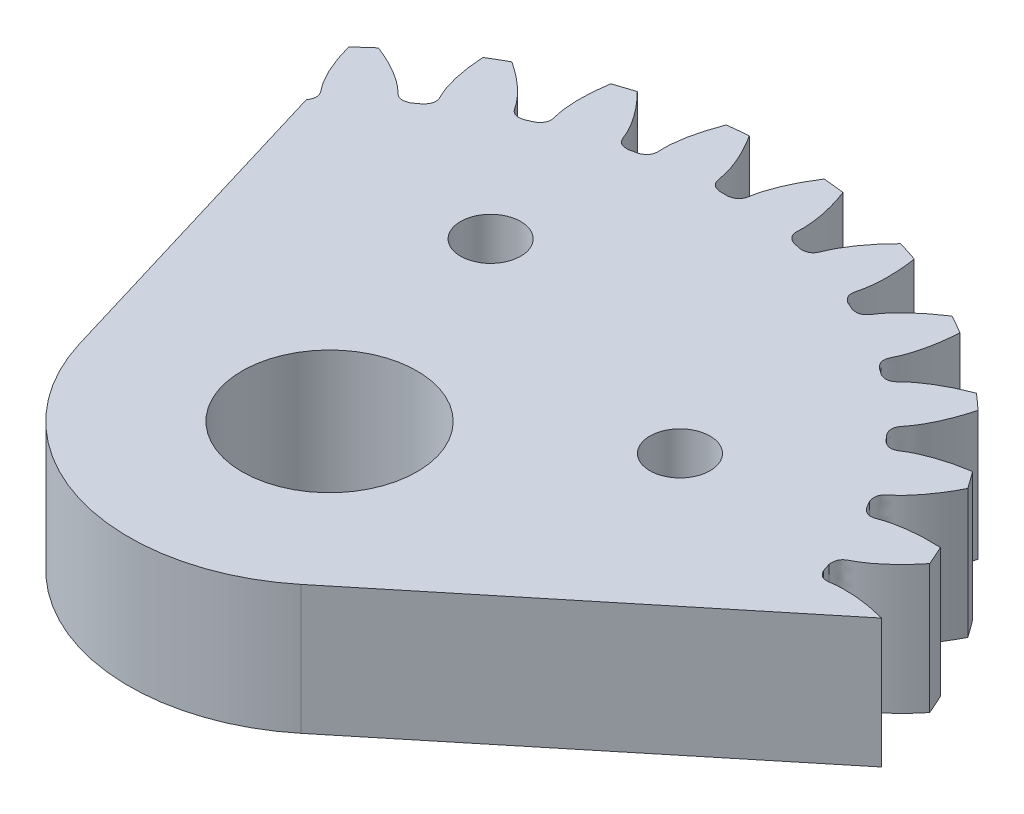
SolidWorks part; units mm, degrees
ref_plane "前视基准面" through (0, 0, 0) normal (0, 0, 1) x (1, 0, 0)
ref_plane "上视基准面" through (0, 0, 0) normal (0, 1, 0) x (1, 0, 0)
ref_plane "右视基准面" through (0, 0, 0) normal (1, 0, 0) x (0, 0, -1)
other "Configuration Table"
sketch "草图2" plane through (0, 0, 0) normal (0, 1, 0) x (1, 0, 0)
  line L0 (-48.308, -1.168) -> (-18.308, -1.168)
  line L1 (-18.308, -1.168) -> (-23.7158, 15.4755) construction
  line L2 (-48.308, -15.168) -> (-18.308, -15.168)
  line L3 (-9.4476, -12.0074) -> (12.8313, 6.2039)
  line L4 (-18.308, -1.168) -> (-4.1502, 9.1183) construction
  line L5 (-12.9002, 15.4755) -> (-18.308, -1.168) construction
  line L6 (-9.558, 13.9875) -> (-18.308, -1.168) construction
  circle A0 centre (-18.308, -1.168) radius 17.5 construction
  circle A1 centre (-23.7158, 15.4755) radius 2.6
  circle A2 centre (-4.1502, 9.1183) radius 2.6
  arc A3 (-16.4787, 16.2362) -> (-9.558, 13.9875) centre (-18.308, -1.168) cw construction
  arc A4 (-8.558, 15.7195) -> (-16.2697, 18.2252) centre (-18.308, -1.168) ccw
  arc A5 (-10.558, 12.2554) -> (-16.6878, 14.2471) centre (-18.308, -1.168) ccw
  arc A6 (-10.558, 12.2554) -> (-8.558, 15.7195) centre (-9.558, 13.9875) ccw
  arc A7 (-16.2697, 18.2252) -> (-16.6878, 14.2471) centre (-16.4787, 16.2362) ccw
  arc A8 (-30.0178, 11.8371) -> (-34.295, 5.9499) centre (-18.308, -1.168) ccw construction
  circle A13 centre (-48.308, -1.168) radius 6.1
  circle A14 centre (-18.308, -1.168) radius 6.1
  arc A15 (-38.5485, 17.4484) -> (-42.2679, 12.3292) centre (-18.308, -1.168) ccw
  arc A16 (-45.091, 12.4574) -> (-48.308, -15.168) centre (-48.308, -1.168) ccw
  arc A17 (-18.308, -15.168) -> (-9.4476, -12.0074) centre (-18.308, -1.168) ccw
  arc A18 (7.9346, 7.0527) -> (7.7547, 7.6064) centre (-18.308, -1.168) ccw
  arc A19 (11.2173, 11.1713) -> (10.6182, 12.517) centre (-18.308, -1.168) ccw
  arc A20 (5.652, 12.3292) -> (5.3608, 12.8334) centre (-18.308, -1.168) ccw
  arc A21 (8.0067, 17.0403) -> (7.1408, 18.2321) centre (-18.308, -1.168) ccw
  arc A22 (2.3222, 17.0158) -> (1.9326, 17.4484) centre (-18.308, -1.168) ccw
  arc A23 (3.6459, 22.1135) -> (2.5512, 23.0992) centre (-18.308, -1.168) ccw
  arc A24 (-1.9093, 20.9076) -> (-2.3803, 21.2499) centre (-18.308, -1.168) ccw
  arc A25 (-1.6743, 26.1692) -> (-2.9501, 26.9058) centre (-18.308, -1.168) ccw
  arc A26 (-6.8574, 23.8347) -> (-7.3893, 24.0715) centre (-18.308, -1.168) ccw
  arc A27 (-7.7215, 29.0302) -> (-9.1226, 29.4854) centre (-18.308, -1.168) ccw
  arc A28 (-12.306, 25.6691) -> (-12.8755, 25.7901) centre (-18.308, -1.168) ccw
  arc A29 (-14.2314, 30.5713) -> (-15.6965, 30.7253) centre (-18.308, -1.168) ccw
  arc A30 (-18.0168, 26.3305) -> (-18.5991, 26.3305) centre (-18.308, -1.168) ccw
  arc A31 (-20.9195, 30.7253) -> (-22.3845, 30.5713) centre (-18.308, -1.168) ccw
  arc A32 (-23.7405, 25.7901) -> (-24.31, 25.6691) centre (-18.308, -1.168) ccw
  arc A33 (-27.4934, 29.4854) -> (-28.8944, 29.0302) centre (-18.308, -1.168) ccw
  arc A34 (-29.2266, 24.0715) -> (-29.7585, 23.8347) centre (-18.308, -1.168) ccw
  arc A35 (-33.6658, 26.9058) -> (-34.9416, 26.1692) centre (-18.308, -1.168) ccw
  arc A36 (-34.2356, 21.2499) -> (-34.7067, 20.9076) centre (-18.308, -1.168) ccw
  arc A37 (-39.1671, 23.0992) -> (-40.2619, 22.1135) centre (-18.308, -1.168) ccw
  spline S0 degree 3 poles (-42.2679, 12.3292) (-42.741, 11.7647) (-43.1486, 11.9953) (-43.6155, 12.1524) (-43.7123, 12.183) (-43.8205, 12.2147) (-43.9402, 12.2473) (-44.0714, 12.2802) (-44.2143, 12.313) (-44.3689, 12.3453) (-44.5351, 12.3765) (-44.7131, 12.4063) (-44.8996, 12.4337) (-45.027, 12.4499) (-45.091, 12.4574) knots 0.548501 0.548501 0.548501 0.548501 0.663825 0.671913 0.681013 0.691124 0.702246 0.714378 0.727522 0.741677 0.756843 0.77302 0.790209 0.807551 0.807551 0.807551 0.807551
  spline S1 degree 3 poles (12.8313, 6.2039) (12.7024, 6.2383) (12.4819, 6.2939) (12.1722, 6.3643) (11.9071, 6.419) (11.6521, 6.4664) (11.4073, 6.5068) (11.1729, 6.5407) (10.9491, 6.5685) (10.736, 6.5906) (10.5337, 6.6076) (10.3424, 6.6198) (10.1621, 6.6276) (9.993, 6.6316) (9.8351, 6.6322) (9.6886, 6.6298) (9.5533, 6.6249) (9.4295, 6.618) (9.317, 6.6094) (9.216, 6.5996) (8.7267, 6.543) (8.28, 6.4022) (7.9346, 7.0527) knots 0 0 0 0 0.035889 0.061166 0.085431 0.108685 0.130929 0.152161 0.172382 0.191592 0.209791 0.22698 0.243157 0.258323 0.272478 0.285622 0.297754 0.308876 0.318987 0.328087 0.336175 0.451499 0.451499 0.451499 0.451499
  spline S2 degree 3 poles (7.7547, 7.6064) (7.6518, 8.3356) (8.0959, 8.4843) (8.5251, 8.7261) (8.6125, 8.7776) (8.7085, 8.8368) (8.8128, 8.9039) (8.9251, 8.9794) (9.0451, 9.0637) (9.1725, 9.1569) (9.307, 9.2596) (9.4482, 9.3719) (9.5958, 9.4942) (9.7495, 9.6268) (9.9089, 9.77) (10.0736, 9.9241) (10.2433, 10.0892) (10.4176, 10.2658) (10.6607, 10.5222) (10.9298, 10.8238) (11.1332, 11.0677) (11.2173, 11.1713) knots 0.548501 0.548501 0.548501 0.548501 0.663825 0.671913 0.681013 0.691124 0.702246 0.714378 0.727522 0.741677 0.756843 0.77302 0.790209 0.808408 0.827618 0.847839 0.869071 0.891315 0.914569 0.964111 1 1 1 1
  spline S3 degree 3 poles (10.6182, 12.517) (10.4849, 12.5239) (10.2576, 12.5324) (9.9401, 12.5369) (9.6694, 12.5353) (9.4101, 12.5286) (9.1623, 12.5172) (8.926, 12.5016) (8.7013, 12.4823) (8.4882, 12.4597) (8.2868, 12.4342) (8.0972, 12.4063) (7.9192, 12.3765) (7.753, 12.3453) (7.5984, 12.313) (7.4555, 12.2802) (7.3243, 12.2473) (7.2046, 12.2147) (7.0964, 12.183) (6.9996, 12.1524) (6.5327, 11.9953) (6.125, 11.7647) (5.652, 12.3292) knots 0 0 0 0 0.035889 0.061166 0.085431 0.108685 0.130929 0.152161 0.172382 0.191592 0.209791 0.22698 0.243157 0.258323 0.272478 0.285622 0.297754 0.308876 0.318987 0.328087 0.336175 0.451499 0.451499 0.451499 0.451499
  spline S4 degree 3 poles (5.3608, 12.8334) (5.1086, 13.5253) (5.5121, 13.763) (5.8816, 14.0888) (5.9565, 14.1573) (6.0381, 14.2352) (6.1261, 14.3225) (6.2203, 14.4198) (6.3201, 14.5271) (6.4253, 14.6448) (6.5355, 14.7732) (6.6503, 14.9124) (6.7692, 15.0627) (6.892, 15.2244) (7.0181, 15.3976) (7.1472, 15.5825) (7.2789, 15.7794) (7.4127, 15.9883) (7.5972, 16.2897) (7.7976, 16.6406) (7.9459, 16.9215) (8.0067, 17.0403) knots 0.548501 0.548501 0.548501 0.548501 0.663825 0.671913 0.681013 0.691124 0.702246 0.714378 0.727522 0.741677 0.756843 0.77302 0.790209 0.808408 0.827618 0.847839 0.869071 0.891315 0.914569 0.964111 1 1 1 1
  spline S5 degree 3 poles (7.1408, 18.2321) (7.009, 18.211) (6.7849, 18.1722) (6.4734, 18.1105) (6.209, 18.0527) (5.9567, 17.9922) (5.7167, 17.9296) (5.4888, 17.8652) (5.273, 17.7995) (5.0693, 17.7331) (4.8776, 17.6663) (4.6979, 17.5996) (4.53, 17.5335) (4.3739, 17.4684) (4.2294, 17.4047) (4.0965, 17.3429) (3.9749, 17.2834) (3.8646, 17.2267) (3.7654, 17.1731) (3.6771, 17.1231) (3.2531, 16.8723) (2.9023, 16.562) (2.3222, 17.0158) knots 0 0 0 0 0.035889 0.061166 0.085431 0.108685 0.130929 0.152161 0.172382 0.191592 0.209791 0.22698 0.243157 0.258323 0.272478 0.285622 0.297754 0.308876 0.318987 0.328087 0.336175 0.451499 0.451499 0.451499 0.451499
  spline S6 degree 3 poles (1.9326, 17.4484) (1.542, 18.0728) (1.8872, 18.3892) (2.1809, 18.7847) (2.2399, 18.8673) (2.3036, 18.9604) (2.3715, 19.0642) (2.4434, 19.1788) (2.5187, 19.3046) (2.5972, 19.4416) (2.6783, 19.5901) (2.7616, 19.7501) (2.8467, 19.9219) (2.9331, 20.1056) (3.0205, 20.3012) (3.1084, 20.5089) (3.1962, 20.7288) (3.2836, 20.961) (3.4015, 21.2941) (3.5245, 21.6791) (3.6112, 21.9847) (3.6459, 22.1135) knots 0.548501 0.548501 0.548501 0.548501 0.663825 0.671913 0.681013 0.691124 0.702246 0.714378 0.727522 0.741677 0.756843 0.77302 0.790209 0.808408 0.827618 0.847839 0.869071 0.891315 0.914569 0.964111 1 1 1 1
  spline S7 degree 3 poles (2.5512, 23.0992) (2.4267, 23.0512) (2.2156, 22.9667) (1.9236, 22.8416) (1.677, 22.73) (1.4429, 22.6184) (1.2211, 22.5072) (1.0116, 22.3969) (0.8141, 22.2878) (0.6287, 22.1805) (0.4551, 22.0753) (0.2932, 21.9727) (0.1427, 21.8731) (0.0035, 21.7769) (-0.1245, 21.6846) (-0.2417, 21.5965) (-0.3483, 21.5131) (-0.4444, 21.4346) (-0.5303, 21.3616) (-0.6063, 21.2943) (-0.9689, 20.9609) (-1.2475, 20.5844) (-1.9093, 20.9076) knots 0 0 0 0 0.035889 0.061166 0.085431 0.108685 0.130929 0.152161 0.172382 0.191592 0.209791 0.22698 0.243157 0.258323 0.272478 0.285622 0.297754 0.308876 0.318987 0.328087 0.336175 0.451499 0.451499 0.451499 0.451499
  spline S8 degree 3 poles (-2.3803, 21.2499) (-2.8922, 21.7794) (-2.6203, 22.1607) (-2.4152, 22.6086) (-2.3747, 22.7016) (-2.3318, 22.8059) (-2.2869, 22.9216) (-2.2404, 23.0487) (-2.1929, 23.1873) (-2.1446, 23.3377) (-2.0962, 23.4997) (-2.048, 23.6736) (-2.0004, 23.8593) (-1.954, 24.0569) (-1.9092, 24.2665) (-1.8665, 24.4879) (-1.8263, 24.7213) (-1.7891, 24.9666) (-1.7431, 25.3169) (-1.7027, 25.7191) (-1.6815, 26.036) (-1.6743, 26.1692) knots 0.548501 0.548501 0.548501 0.548501 0.663825 0.671913 0.681013 0.691124 0.702246 0.714378 0.727522 0.741677 0.756843 0.77302 0.790209 0.808408 0.827618 0.847839 0.869071 0.891315 0.914569 0.964111 1 1 1 1
  spline S9 degree 3 poles (-2.9501, 26.9058) (-3.0619, 26.833) (-3.2508, 26.7063) (-3.5104, 26.5233) (-3.7284, 26.3629) (-3.9342, 26.2051) (-4.128, 26.0502) (-4.31, 25.8987) (-4.4804, 25.751) (-4.6395, 25.6074) (-4.7875, 25.4684) (-4.9245, 25.3344) (-5.051, 25.2057) (-5.1671, 25.0827) (-5.2732, 24.9658) (-5.3695, 24.8553) (-5.4564, 24.7515) (-5.5341, 24.6548) (-5.6029, 24.5655) (-5.6633, 24.4838) (-5.9486, 24.0823) (-6.1429, 23.6562) (-6.8574, 23.8347) knots 0 0 0 0 0.035889 0.061166 0.085431 0.108685 0.130929 0.152161 0.172382 0.191592 0.209791 0.22698 0.243157 0.258323 0.272478 0.285622 0.297754 0.308876 0.318987 0.328087 0.336175 0.451499 0.451499 0.451499 0.451499
  spline S10 degree 3 poles (-7.3893, 24.0715) (-8.0001, 24.483) (-7.8134, 24.9125) (-7.7059, 25.3933) (-7.6856, 25.4927) (-7.6654, 25.6037) (-7.6455, 25.7261) (-7.6265, 25.8601) (-7.6088, 26.0056) (-7.5928, 26.1627) (-7.5791, 26.3313) (-7.5681, 26.5114) (-7.5602, 26.703) (-7.556, 26.9059) (-7.5557, 27.1202) (-7.56, 27.3457) (-7.5692, 27.5823) (-7.5838, 27.83) (-7.6116, 28.1822) (-7.6557, 28.5839) (-7.7008, 28.8984) (-7.7215, 29.0302) knots 0.548501 0.548501 0.548501 0.548501 0.663825 0.671913 0.681013 0.691124 0.702246 0.714378 0.727522 0.741677 0.756843 0.77302 0.790209 0.808408 0.827618 0.847839 0.869071 0.891315 0.914569 0.964111 1 1 1 1
  spline S11 degree 3 poles (-9.1226, 29.4854) (-9.2168, 29.3909) (-9.3752, 29.2278) (-9.5911, 28.9948) (-9.771, 28.7926) (-9.9395, 28.5954) (-10.0969, 28.4036) (-10.2434, 28.2176) (-10.3794, 28.0376) (-10.5051, 27.8641) (-10.6209, 27.6974) (-10.7272, 27.5378) (-10.8241, 27.3857) (-10.9121, 27.2412) (-10.9916, 27.1048) (-11.0628, 26.9766) (-11.1262, 26.8571) (-11.182, 26.7463) (-11.2308, 26.6447) (-11.2729, 26.5523) (-11.4685, 26.1002) (-11.57, 25.643) (-12.306, 25.6691) knots 0 0 0 0 0.035889 0.061166 0.085431 0.108685 0.130929 0.152161 0.172382 0.191592 0.209791 0.22698 0.243157 0.258323 0.272478 0.285622 0.297754 0.308876 0.318987 0.328087 0.336175 0.451499 0.451499 0.451499 0.451499
  spline S12 degree 3 poles (-12.8755, 25.7901) (-13.5585, 26.0656) (-13.4651, 26.5246) (-13.46, 27.0172) (-13.4608, 27.1186) (-13.4641, 27.2314) (-13.4701, 27.3553) (-13.4793, 27.4903) (-13.4923, 27.6363) (-13.5094, 27.7933) (-13.531, 27.961) (-13.5577, 28.1395) (-13.5898, 28.3285) (-13.6278, 28.5279) (-13.6721, 28.7375) (-13.7232, 28.9572) (-13.7814, 29.1868) (-13.8471, 29.426) (-13.9476, 29.7648) (-14.0743, 30.1485) (-14.1838, 30.4467) (-14.2314, 30.5713) knots 0.548501 0.548501 0.548501 0.548501 0.663825 0.671913 0.681013 0.691124 0.702246 0.714378 0.727522 0.741677 0.756843 0.77302 0.790209 0.808408 0.827618 0.847839 0.869071 0.891315 0.914569 0.964111 1 1 1 1
  spline S13 degree 3 poles (-15.6965, 30.7253) (-15.769, 30.6133) (-15.8901, 30.4208) (-16.0527, 30.148) (-16.1867, 29.9128) (-16.3105, 29.6849) (-16.4246, 29.4646) (-16.5292, 29.2521) (-16.6248, 29.0479) (-16.7117, 28.852) (-16.7904, 28.6649) (-16.8611, 28.4867) (-16.9243, 28.3177) (-16.9803, 28.1581) (-17.0297, 28.0081) (-17.0727, 27.868) (-17.1098, 27.7378) (-17.1415, 27.6179) (-17.1681, 27.5083) (-17.19, 27.4092) (-17.2874, 26.9263) (-17.2915, 26.458) (-18.0168, 26.3305) knots 0 0 0 0 0.035889 0.061166 0.085431 0.108685 0.130929 0.152161 0.172382 0.191592 0.209791 0.22698 0.243157 0.258323 0.272478 0.285622 0.297754 0.308876 0.318987 0.328087 0.336175 0.451499 0.451499 0.451499 0.451499
  spline S14 degree 3 poles (-18.5991, 26.3305) (-19.3244, 26.458) (-19.3286, 26.9263) (-19.4259, 27.4092) (-19.4479, 27.5083) (-19.4745, 27.6179) (-19.5061, 27.7378) (-19.5432, 27.868) (-19.5863, 28.0081) (-19.6356, 28.1581) (-19.6917, 28.3177) (-19.7548, 28.4867) (-19.8256, 28.6649) (-19.9042, 28.852) (-19.9911, 29.0479) (-20.0867, 29.2521) (-20.1914, 29.4646) (-20.3054, 29.6849) (-20.4741, 29.9954) (-20.6778, 30.3444) (-20.8469, 30.6133) (-20.9195, 30.7253) knots 0.548501 0.548501 0.548501 0.548501 0.663825 0.671913 0.681013 0.691124 0.702246 0.714378 0.727522 0.741677 0.756843 0.77302 0.790209 0.808408 0.827618 0.847839 0.869071 0.891315 0.914569 0.964111 1 1 1 1
  spline S15 degree 3 poles (-22.3845, 30.5713) (-22.4322, 30.4467) (-22.5106, 30.2332) (-22.613, 29.9325) (-22.6951, 29.6747) (-22.7688, 29.426) (-22.8346, 29.1868) (-22.8928, 28.9572) (-22.9438, 28.7375) (-22.9881, 28.5279) (-23.0261, 28.3285) (-23.0583, 28.1395) (-23.0849, 27.961) (-23.1066, 27.7933) (-23.1237, 27.6363) (-23.1366, 27.4903) (-23.1459, 27.3553) (-23.1519, 27.2314) (-23.1551, 27.1186) (-23.156, 27.0172) (-23.1508, 26.5246) (-23.0575, 26.0656) (-23.7405, 25.7901) knots 0 0 0 0 0.035889 0.061166 0.085431 0.108685 0.130929 0.152161 0.172382 0.191592 0.209791 0.22698 0.243157 0.258323 0.272478 0.285622 0.297754 0.308876 0.318987 0.328087 0.336175 0.451499 0.451499 0.451499 0.451499
  spline S16 degree 3 poles (-24.31, 25.6691) (-25.046, 25.643) (-25.1474, 26.1002) (-25.343, 26.5523) (-25.3851, 26.6447) (-25.4339, 26.7463) (-25.4898, 26.8571) (-25.5531, 26.9766) (-25.6244, 27.1048) (-25.7038, 27.2412) (-25.7918, 27.3857) (-25.8888, 27.5378) (-25.995, 27.6974) (-26.1108, 27.8641) (-26.2366, 28.0376) (-26.3725, 28.2176) (-26.5191, 28.4036) (-26.6765, 28.5954) (-26.906, 28.864) (-27.1778, 29.1631) (-27.3992, 29.3909) (-27.4934, 29.4854) knots 0.548501 0.548501 0.548501 0.548501 0.663825 0.671913 0.681013 0.691124 0.702246 0.714378 0.727522 0.741677 0.756843 0.77302 0.790209 0.808408 0.827618 0.847839 0.869071 0.891315 0.914569 0.964111 1 1 1 1
  spline S17 degree 3 poles (-28.8944, 29.0302) (-28.9151, 28.8984) (-28.9474, 28.6732) (-28.9851, 28.3579) (-29.0118, 28.0885) (-29.0322, 27.83) (-29.0468, 27.5823) (-29.056, 27.3457) (-29.0602, 27.1202) (-29.06, 26.9059) (-29.0557, 26.703) (-29.0478, 26.5114) (-29.0368, 26.3313) (-29.0231, 26.1627) (-29.0072, 26.0056) (-28.9895, 25.8601) (-28.9705, 25.7261) (-28.9506, 25.6037) (-28.9303, 25.4927) (-28.91, 25.3933) (-28.8026, 24.9125) (-28.6159, 24.483) (-29.2266, 24.0715) knots 0 0 0 0 0.035889 0.061166 0.085431 0.108685 0.130929 0.152161 0.172382 0.191592 0.209791 0.22698 0.243157 0.258323 0.272478 0.285622 0.297754 0.308876 0.318987 0.328087 0.336175 0.451499 0.451499 0.451499 0.451499
  spline S18 degree 3 poles (-29.7585, 23.8347) (-30.473, 23.6562) (-30.6673, 24.0823) (-30.9527, 24.4838) (-31.013, 24.5655) (-31.0819, 24.6548) (-31.1596, 24.7515) (-31.2464, 24.8553) (-31.3427, 24.9658) (-31.4488, 25.0827) (-31.5649, 25.2057) (-31.6914, 25.3344) (-31.8285, 25.4684) (-31.9764, 25.6074) (-32.1355, 25.751) (-32.3059, 25.8987) (-32.4879, 26.0502) (-32.6817, 26.2051) (-32.9621, 26.4201) (-33.2902, 26.6561) (-33.554, 26.833) (-33.6658, 26.9058) knots 0.548501 0.548501 0.548501 0.548501 0.663825 0.671913 0.681013 0.691124 0.702246 0.714378 0.727522 0.741677 0.756843 0.77302 0.790209 0.808408 0.827618 0.847839 0.869071 0.891315 0.914569 0.964111 1 1 1 1
  spline S19 degree 3 poles (-34.9416, 26.1692) (-34.9345, 26.036) (-34.9192, 25.8091) (-34.8905, 25.4928) (-34.8606, 25.2238) (-34.8268, 24.9666) (-34.7896, 24.7213) (-34.7494, 24.4879) (-34.7067, 24.2665) (-34.6619, 24.0569) (-34.6155, 23.8593) (-34.568, 23.6736) (-34.5198, 23.4997) (-34.4713, 23.3377) (-34.4231, 23.1873) (-34.3755, 23.0487) (-34.3291, 22.9216) (-34.2842, 22.8059) (-34.2412, 22.7016) (-34.2007, 22.6086) (-33.9957, 22.1607) (-33.7238, 21.7794) (-34.2356, 21.2499) knots 0 0 0 0 0.035889 0.061166 0.085431 0.108685 0.130929 0.152161 0.172382 0.191592 0.209791 0.22698 0.243157 0.258323 0.272478 0.285622 0.297754 0.308876 0.318987 0.328087 0.336175 0.451499 0.451499 0.451499 0.451499
  spline S20 degree 3 poles (-34.7067, 20.9076) (-35.3684, 20.5844) (-35.6471, 20.9609) (-36.0097, 21.2943) (-36.0856, 21.3616) (-36.1716, 21.4346) (-36.2677, 21.5131) (-36.3742, 21.5965) (-36.4914, 21.6846) (-36.6195, 21.7769) (-36.7586, 21.8731) (-36.9091, 21.9727) (-37.071, 22.0753) (-37.2446, 22.1805) (-37.4301, 22.2878) (-37.6275, 22.3969) (-37.837, 22.5072) (-38.0588, 22.6184) (-38.3778, 22.7705) (-38.7477, 22.9331) (-39.0426, 23.0512) (-39.1671, 23.0992) knots 0.548501 0.548501 0.548501 0.548501 0.663825 0.671913 0.681013 0.691124 0.702246 0.714378 0.727522 0.741677 0.756843 0.77302 0.790209 0.808408 0.827618 0.847839 0.869071 0.891315 0.914569 0.964111 1 1 1 1
  spline S21 degree 3 poles (-40.2619, 22.1135) (-40.2271, 21.9847) (-40.1651, 21.7659) (-40.0712, 21.4625) (-39.9861, 21.2056) (-39.8995, 20.961) (-39.8121, 20.7288) (-39.7243, 20.5089) (-39.6365, 20.3012) (-39.5491, 20.1056) (-39.4626, 19.9219) (-39.3775, 19.7501) (-39.2942, 19.5901) (-39.2131, 19.4416) (-39.1347, 19.3046) (-39.0593, 19.1788) (-38.9874, 19.0642) (-38.9195, 18.9604) (-38.8558, 18.8673) (-38.7969, 18.7847) (-38.5032, 18.3892) (-38.1579, 18.0728) (-38.5485, 17.4484) knots 0 0 0 0 0.035889 0.061166 0.085431 0.108685 0.130929 0.152161 0.172382 0.191592 0.209791 0.22698 0.243157 0.258323 0.272478 0.285622 0.297754 0.308876 0.318987 0.328087 0.336175 0.451499 0.451499 0.451499 0.451499
  point P32 (-12.9002, 15.4755)
  point P65 (-32.4658, 9.1183)
  dimension "D1" = 35
  dimension "D3" = 5.2
  dimension "D5" = 5.2
  dimension "D7" = 2
  dimension "D2" = 72
  dimension "D4" = 72
  dimension "D6" = 36
  dimension "D8" = 12
extrude "凸台-拉伸1" add sketch "草图2" along normal blind 9 contours A37 S21 A15 S0 A16 L2 A17 L3 S1 A18 S2 A19 S3 A20 S4 A21 S5 A22 S6 A23 S7 A24 S8 A25 S9 A26 S10 A27 S11 A28 S12 A29 S13 A30 S14 A31 S15 A32 S16 A33 S17 A34 S18 A35 S19 A36 S20 region at (-25.179, 0, -5.1379)
sketch "草图3" plane through (0, 9, 0) normal (0, 1, 0) x (1, 0, 0)
  line L0 (-38.5485, 17.4484) -> (-31.7111, -5.2121)
  line L2 (-48.308, -15.168) -> (-18.308, -15.168)
  line L3 (-9.4476, -12.0074) -> (12.8313, 6.2039)
  line L4 (-48.308, -15.168) -> (-18.308, -15.168)
  line L5 (-9.4476, -12.0074) -> (12.8313, 6.2039)
  circle A0 centre (-18.308, -1.168) radius 6.1 construction
  circle A1 centre (-18.308, -1.168) radius 6.1
  circle A2 centre (-18.308, -1.168) radius 14
  arc A23 (-39.1671, 23.0992) -> (-40.2619, 22.1135) centre (-18.308, -1.168) ccw
  arc A24 (-38.5485, 17.4484) -> (-42.2679, 12.3292) centre (-18.308, -1.168) ccw
  arc A25 (-45.091, 12.4574) -> (-48.308, -15.168) centre (-48.308, -1.168) ccw
  arc A26 (-18.308, -15.168) -> (-9.4476, -12.0074) centre (-18.308, -1.168) ccw
  arc A27 (7.9346, 7.0527) -> (7.7547, 7.6064) centre (-18.308, -1.168) ccw
  arc A28 (11.2173, 11.1713) -> (10.6182, 12.517) centre (-18.308, -1.168) ccw
  arc A29 (5.652, 12.3292) -> (5.3608, 12.8334) centre (-18.308, -1.168) ccw
  arc A30 (8.0067, 17.0403) -> (7.1408, 18.2321) centre (-18.308, -1.168) ccw
  arc A31 (2.3222, 17.0158) -> (1.9326, 17.4484) centre (-18.308, -1.168) ccw
  arc A32 (3.6459, 22.1135) -> (2.5512, 23.0992) centre (-18.308, -1.168) ccw
  arc A33 (-1.9093, 20.9076) -> (-2.3803, 21.2499) centre (-18.308, -1.168) ccw
  arc A34 (-1.6743, 26.1692) -> (-2.9501, 26.9058) centre (-18.308, -1.168) ccw
  arc A35 (-6.8574, 23.8347) -> (-7.3893, 24.0715) centre (-18.308, -1.168) ccw
  arc A36 (-7.7215, 29.0302) -> (-9.1226, 29.4854) centre (-18.308, -1.168) ccw
  arc A37 (-12.306, 25.6691) -> (-12.8755, 25.7901) centre (-18.308, -1.168) ccw
  arc A38 (-14.2314, 30.5713) -> (-15.6965, 30.7253) centre (-18.308, -1.168) ccw
  arc A39 (-18.0168, 26.3305) -> (-18.5991, 26.3305) centre (-18.308, -1.168) ccw
  arc A40 (-20.9195, 30.7253) -> (-22.3845, 30.5713) centre (-18.308, -1.168) ccw
  arc A41 (-23.7405, 25.7901) -> (-24.31, 25.6691) centre (-18.308, -1.168) ccw
  arc A42 (-27.4934, 29.4854) -> (-28.8944, 29.0302) centre (-18.308, -1.168) ccw
  arc A43 (-29.2266, 24.0715) -> (-29.7585, 23.8347) centre (-18.308, -1.168) ccw
  arc A44 (-33.6658, 26.9058) -> (-34.9416, 26.1692) centre (-18.308, -1.168) ccw
  arc A45 (-34.2356, 21.2499) -> (-34.7067, 20.9076) centre (-18.308, -1.168) ccw
  arc A46 (-39.1671, 23.0992) -> (-40.2619, 22.1135) centre (-18.308, -1.168) ccw
  arc A47 (-38.5485, 17.4484) -> (-42.2679, 12.3292) centre (-18.308, -1.168) ccw
  arc A48 (-45.091, 12.4574) -> (-48.308, -15.168) centre (-48.308, -1.168) ccw
  arc A49 (-18.308, -15.168) -> (-9.4476, -12.0074) centre (-18.308, -1.168) ccw
  arc A50 (7.9346, 7.0527) -> (7.7547, 7.6064) centre (-18.308, -1.168) ccw
  arc A51 (11.2173, 11.1713) -> (10.6182, 12.517) centre (-18.308, -1.168) ccw
  arc A52 (5.652, 12.3292) -> (5.3608, 12.8334) centre (-18.308, -1.168) ccw
  arc A53 (8.0067, 17.0403) -> (7.1408, 18.2321) centre (-18.308, -1.168) ccw
  arc A54 (2.3222, 17.0158) -> (1.9326, 17.4484) centre (-18.308, -1.168) ccw
  arc A55 (3.6459, 22.1135) -> (2.5512, 23.0992) centre (-18.308, -1.168) ccw
  arc A56 (-1.9093, 20.9076) -> (-2.3803, 21.2499) centre (-18.308, -1.168) ccw
  arc A57 (-1.6743, 26.1692) -> (-2.9501, 26.9058) centre (-18.308, -1.168) ccw
  arc A58 (-6.8574, 23.8347) -> (-7.3893, 24.0715) centre (-18.308, -1.168) ccw
  arc A59 (-7.7215, 29.0302) -> (-9.1226, 29.4854) centre (-18.308, -1.168) ccw
  arc A60 (-12.306, 25.6691) -> (-12.8755, 25.7901) centre (-18.308, -1.168) ccw
  arc A61 (-14.2314, 30.5713) -> (-15.6965, 30.7253) centre (-18.308, -1.168) ccw
  arc A62 (-18.0168, 26.3305) -> (-18.5991, 26.3305) centre (-18.308, -1.168) ccw
  arc A63 (-20.9195, 30.7253) -> (-22.3845, 30.5713) centre (-18.308, -1.168) ccw
  arc A64 (-23.7405, 25.7901) -> (-24.31, 25.6691) centre (-18.308, -1.168) ccw
  arc A65 (-27.4934, 29.4854) -> (-28.8944, 29.0302) centre (-18.308, -1.168) ccw
  arc A66 (-29.2266, 24.0715) -> (-29.7585, 23.8347) centre (-18.308, -1.168) ccw
  arc A67 (-33.6658, 26.9058) -> (-34.9416, 26.1692) centre (-18.308, -1.168) ccw
  arc A68 (-34.2356, 21.2499) -> (-34.7067, 20.9076) centre (-18.308, -1.168) ccw
  spline S22 degree 3 poles (-2808.7731, -2864.6652) (154.4229, 178.0688) (-54.0437, 66.6203) (-40.0712, 21.4625) (-39.9861, 21.2056) (-39.8995, 20.961) (-39.8121, 20.7288) (-39.7243, 20.5089) (-39.6365, 20.3012) (-39.5491, 20.1056) (-39.4626, 19.9219) (-39.3775, 19.7501) (-39.2942, 19.5901) (-39.2131, 19.4416) (-39.1347, 19.3046) (-39.0593, 19.1788) (-38.9874, 19.0642) (-38.9195, 18.9604) (-38.8558, 18.8673) (-38.7969, 18.7847) (-34.47, 12.9588) (-12.3892, 20.0165) (-3637.1494, -1726.3063) knots -12.628781 -12.628781 -12.628781 -12.628781 0.035889 0.061166 0.085431 0.108685 0.130929 0.152161 0.172382 0.191592 0.209791 0.22698 0.243157 0.258323 0.272478 0.285622 0.297754 0.308876 0.318987 0.328087 0.336175 2.271088 2.271088 2.271088 2.271088 only from (-40.2619, 22.1135) to (-38.5485, 17.4484)
  spline S23 degree 3 poles (504.2173, 3974.4238) (-36.6266, -13.3464) (-36.7373, 9.8375) (-43.6155, 12.1524) (-43.7123, 12.183) (-43.8205, 12.2147) (-43.9402, 12.2473) (-44.0714, 12.2802) (-44.2143, 12.313) (-44.3689, 12.3453) (-44.5351, 12.3765) (-44.7131, 12.4063) (-77.1597, 17.1715) (-131.5858, -139.3296) (1832.491, 3544.1954) knots -1.271213 -1.271213 -1.271213 -1.271213 0.663825 0.671913 0.681013 0.691124 0.702246 0.714378 0.727522 0.741677 0.756843 0.77302 0.790209 9.577619 9.577619 9.577619 9.577619 only from (-42.2679, 12.3292) to (-45.091, 12.4574)
  spline S24 degree 3 poles (-1102.9367, 3847.1943) (50.5502, -240.3757) (58.2663, -4.114) (12.1722, 6.3643) (11.9071, 6.419) (11.6521, 6.4664) (11.4073, 6.5068) (11.1729, 6.5407) (10.9491, 6.5685) (10.736, 6.5906) (10.5337, 6.6076) (10.3424, 6.6198) (10.1621, 6.6276) (9.993, 6.6316) (9.8351, 6.6322) (9.6886, 6.6298) (9.5533, 6.6249) (9.4295, 6.618) (9.317, 6.6094) (9.216, 6.5996) (2.0072, 5.7654) (-2.921, -16.886) (297.0991, 3995.4098) knots -12.628781 -12.628781 -12.628781 -12.628781 0.035889 0.061166 0.085431 0.108685 0.130929 0.152161 0.172382 0.191592 0.209791 0.22698 0.243157 0.258323 0.272478 0.285622 0.297754 0.308876 0.318987 0.328087 0.336175 2.271088 2.271088 2.271088 2.271088 only from (12.8313, 6.2039) to (7.9346, 7.0527)
  spline S25 degree 3 poles (2586.3817, -3049.5365) (-15.1002, 20.5939) (2.2024, 5.1636) (8.5251, 8.7261) (8.6125, 8.7776) (8.7085, 8.8368) (8.8128, 8.9039) (8.9251, 8.9794) (9.0451, 9.0637) (9.1725, 9.1569) (9.307, 9.2596) (9.4482, 9.3719) (9.5958, 9.4942) (9.7495, 9.6268) (9.9089, 9.77) (10.0736, 9.9241) (10.2433, 10.0892) (10.4176, 10.2658) (10.6607, 10.5222) (42.3769, 46.0814) (-104.8979, 234.9145) (1366.3354, -3752.1377) knots -1.271185 -1.271185 -1.271185 -1.271185 0.663825 0.671913 0.681013 0.691124 0.702246 0.714378 0.727522 0.741677 0.756843 0.77302 0.790209 0.808408 0.827618 0.847839 0.869071 0.891315 0.914569 0.964111 13.705364 13.705364 13.705364 13.705364 only from (7.7547, 7.6064) to (11.2173, 11.1713)
  spline S26 degree 3 poles (-1879.3545, 3537.5914) (98.7795, -220.832) (57.2054, 11.8711) (9.9401, 12.5369) (9.6694, 12.5353) (9.4101, 12.5286) (9.1623, 12.5172) (8.926, 12.5016) (8.7013, 12.4823) (8.4882, 12.4597) (8.2868, 12.4342) (8.0972, 12.4063) (7.9192, 12.3765) (7.753, 12.3453) (7.5984, 12.313) (7.4555, 12.2802) (7.3243, 12.2473) (7.2046, 12.2147) (7.0964, 12.183) (6.9996, 12.1524) (0.1218, 9.8377) (0.0107, -13.3434) (-540.7285, 3973.6518) knots -12.628781 -12.628781 -12.628781 -12.628781 0.035889 0.061166 0.085431 0.108685 0.130929 0.152161 0.172382 0.191592 0.209791 0.22698 0.243157 0.258323 0.272478 0.285622 0.297754 0.308876 0.318987 0.328087 0.336175 2.271088 2.271088 2.271088 2.271088 only from (10.6182, 12.517) to (5.652, 12.3292)
  spline S27 degree 3 poles (3163.2544, -2441.3769) (-19.6949, 20.7853) (0.4378, 9.2896) (5.8816, 14.0888) (5.9565, 14.1573) (6.0381, 14.2352) (6.1261, 14.3225) (6.2203, 14.4198) (6.3201, 14.5271) (6.4253, 14.6448) (6.5355, 14.7732) (6.6503, 14.9124) (6.7692, 15.0627) (6.892, 15.2244) (7.0181, 15.3976) (7.1472, 15.5825) (7.2789, 15.7794) (7.4127, 15.9883) (7.5972, 16.2897) (31.2271, 57.666) (-152.09, 211.7525) (2115.9481, -3382.2865) knots -1.271185 -1.271185 -1.271185 -1.271185 0.663825 0.671913 0.681013 0.691124 0.702246 0.714378 0.727522 0.741677 0.756843 0.77302 0.790209 0.808408 0.827618 0.847839 0.869071 0.891315 0.914569 0.964111 13.705364 13.705364 13.705364 13.705364 only from (5.3608, 12.8334) to (8.0067, 17.0403)
  spline S28 degree 3 poles (-2574.4356, 3073.3277) (141.8916, -191.6879) (52.8443, 27.2862) (6.4734, 18.1105) (6.209, 18.0527) (5.9567, 17.9922) (5.7167, 17.9296) (5.4888, 17.8652) (5.273, 17.7995) (5.0693, 17.7331) (4.8776, 17.6663) (4.6979, 17.5996) (4.53, 17.5335) (4.3739, 17.4684) (4.2294, 17.4047) (4.0965, 17.3429) (3.9749, 17.2834) (3.8646, 17.2267) (3.7654, 17.1731) (3.6771, 17.1231) (-2.5692, 13.4289) (2.1418, -9.2687) (-1355.7239, 3778.1751) knots -12.628781 -12.628781 -12.628781 -12.628781 0.035889 0.061166 0.085431 0.108685 0.130929 0.152161 0.172382 0.191592 0.209791 0.22698 0.243157 0.258323 0.272478 0.285622 0.297754 0.308876 0.318987 0.328087 0.336175 2.271088 2.271088 2.271088 2.271088 only from (7.1408, 18.2321) to (2.3222, 17.0158)
  spline S29 degree 3 poles (3601.0776, -1726.5685) (-24.2289, 20.0172) (-2.1461, 12.9585) (2.1809, 18.7847) (2.2399, 18.8673) (2.3036, 18.9604) (2.3715, 19.0642) (2.4434, 19.1788) (2.5187, 19.3046) (2.5972, 19.4416) (2.6783, 19.5901) (2.7616, 19.7501) (2.8467, 19.9219) (2.9331, 20.1056) (3.0205, 20.3012) (3.1084, 20.5089) (3.1962, 20.7288) (3.2836, 20.961) (3.4015, 21.2941) (17.9124, 66.6792) (-193.4352, 179.2848) (2772.2835, -2864.6642) knots -1.271185 -1.271185 -1.271185 -1.271185 0.663825 0.671913 0.681013 0.691124 0.702246 0.714378 0.727522 0.741677 0.756843 0.77302 0.790209 0.808408 0.827618 0.847839 0.869071 0.891315 0.914569 0.964111 13.705364 13.705364 13.705364 13.705364 only from (1.9326, 17.4484) to (3.6459, 22.1135)
  spline S30 degree 3 poles (-3157.8017, 2474.6938) (178.0022, -154.2173) (45.3735, 41.4578) (1.9236, 22.8416) (1.677, 22.73) (1.4429, 22.6184) (1.2211, 22.5072) (1.0116, 22.3969) (0.8141, 22.2878) (0.6287, 22.1805) (0.4551, 22.0753) (0.2932, 21.9727) (0.1427, 21.8731) (0.0035, 21.7769) (-0.1245, 21.6846) (-0.2417, 21.5965) (-0.3483, 21.5131) (-0.4444, 21.4346) (-0.5303, 21.3616) (-0.6063, 21.2943) (-5.948, 16.3822) (3.3792, -4.8399) (-2112.2677, 3417.523) knots -12.628781 -12.628781 -12.628781 -12.628781 0.035889 0.061166 0.085431 0.108685 0.130929 0.152161 0.172382 0.191592 0.209791 0.22698 0.243157 0.258323 0.272478 0.285622 0.297754 0.308876 0.318987 0.328087 0.336175 2.271088 2.271088 2.271088 2.271088 only from (2.5512, 23.0992) to (-1.9093, 20.9076)
  spline S31 degree 3 poles (3880.7163, -936.3517) (-28.5042, 18.3233) (-5.4363, 16.0101) (-2.4152, 22.6086) (-2.3747, 22.7016) (-2.3318, 22.8059) (-2.2869, 22.9216) (-2.2404, 23.0487) (-2.1929, 23.1873) (-2.1446, 23.3377) (-2.0962, 23.4997) (-2.048, 23.6736) (-2.0004, 23.8593) (-1.954, 24.0569) (-1.9092, 24.2665) (-1.8665, 24.4879) (-1.8263, 24.7213) (-1.7891, 24.9666) (-1.7431, 25.3169) (3.0146, 72.7272) (-227.1265, 138.9304) (3306.6567, -2221.8933) knots -1.271185 -1.271185 -1.271185 -1.271185 0.663825 0.671913 0.681013 0.691124 0.702246 0.714378 0.727522 0.741677 0.756843 0.77302 0.790209 0.808408 0.827618 0.847839 0.869071 0.891315 0.914569 0.964111 13.705364 13.705364 13.705364 13.705364 only from (-2.3803, 21.2499) to (-1.6743, 26.1692)
  spline S32 degree 3 poles (-3603.9568, 1767.8528) (205.5331, -110.0576) (35.1195, 53.7665) (-3.5104, 26.5233) (-3.7284, 26.3629) (-3.9342, 26.2051) (-4.128, 26.0502) (-4.31, 25.8987) (-4.4804, 25.751) (-4.6395, 25.6074) (-4.7875, 25.4684) (-4.9245, 25.3344) (-5.051, 25.2057) (-5.1671, 25.0827) (-5.2732, 24.9658) (-5.3695, 24.8553) (-5.4564, 24.7515) (-5.5341, 24.6548) (-5.6029, 24.5655) (-5.6633, 24.4838) (-9.8669, 18.5685) (3.6687, -0.2506) (-2777.2955, 2907.4577) knots -12.628781 -12.628781 -12.628781 -12.628781 0.035889 0.061166 0.085431 0.108685 0.130929 0.152161 0.172382 0.191592 0.209791 0.22698 0.243157 0.258323 0.272478 0.285622 0.297754 0.308876 0.318987 0.328087 0.336175 2.271088 2.271088 2.271088 2.271088 only from (-2.9501, 26.9058) to (-6.8574, 23.8347)
  spline S33 degree 3 poles (3989.9489, -105.263) (-32.3338, 15.7774) (-9.2891, 18.3109) (-7.7059, 25.3933) (-7.6856, 25.4927) (-7.6654, 25.6037) (-7.6455, 25.7261) (-7.6265, 25.8601) (-7.6088, 26.0056) (-7.5928, 26.1627) (-7.5791, 26.3313) (-7.5681, 26.5114) (-7.5602, 26.703) (-7.556, 26.9059) (-7.5557, 27.1202) (-7.56, 27.3457) (-7.5692, 27.5823) (-7.5838, 27.83) (-7.6116, 28.1822) (-12.815, 75.5457) (-251.6914, 92.4531) (3695.713, -1482.0661) knots -1.271185 -1.271185 -1.271185 -1.271185 0.663825 0.671913 0.681013 0.691124 0.702246 0.714378 0.727522 0.741677 0.756843 0.77302 0.790209 0.808408 0.827618 0.847839 0.869071 0.891315 0.914569 0.964111 13.705364 13.705364 13.705364 13.705364 only from (-7.3893, 24.0715) to (-7.7215, 29.0302)
  spline S34 degree 3 poles (-3893.4019, 983.6971) (223.281, -61.1389) (22.5305, 63.6742) (-9.5911, 28.9948) (-9.771, 28.7926) (-9.9395, 28.5954) (-10.0969, 28.4036) (-10.2434, 28.2176) (-10.3794, 28.0376) (-10.5051, 27.8641) (-10.6209, 27.6974) (-10.7272, 27.5378) (-10.8241, 27.3857) (-10.9121, 27.2412) (-10.9916, 27.1048) (-11.0628, 26.9766) (-11.1262, 26.8571) (-11.182, 26.7463) (-11.2308, 26.6447) (-11.2729, 26.5523) (-14.1548, 19.8922) (2.9977, 4.2985) (-3321.7423, 2270.2715) knots -12.628781 -12.628781 -12.628781 -12.628781 0.035889 0.061166 0.085431 0.108685 0.130929 0.152161 0.172382 0.191592 0.209791 0.22698 0.243157 0.258323 0.272478 0.285622 0.297754 0.308876 0.318987 0.328087 0.336175 2.271088 2.271088 2.271088 2.271088 only from (-9.1226, 29.4854) to (-12.306, 25.6691)
  spline S35 degree 3 poles (3924.0015, 730.3752) (-35.5505, 12.491) (-13.5361, 19.7603) (-13.46, 27.0172) (-13.4608, 27.1186) (-13.4641, 27.2314) (-13.4701, 27.3553) (-13.4793, 27.4903) (-13.4923, 27.6363) (-13.5094, 27.7933) (-13.531, 27.961) (-13.5577, 28.1395) (-13.5898, 28.3285) (-13.6278, 28.5279) (-13.6721, 28.7375) (-13.7232, 28.9572) (-13.7814, 29.1868) (-13.8471, 29.426) (-13.9476, 29.7648) (-28.8847, 75.0113) (-266.0564, 41.8842) (3922.4488, -677.5165) knots -1.271185 -1.271185 -1.271185 -1.271185 0.663825 0.671913 0.681013 0.691124 0.702246 0.714378 0.727522 0.741677 0.756843 0.77302 0.790209 0.808408 0.827618 0.847839 0.869071 0.891315 0.914569 0.964111 13.705364 13.705364 13.705364 13.705364 only from (-12.8755, 25.7901) to (-14.2314, 30.5713)
  spline S36 degree 3 poles (-4013.4867, 156.4981) (230.4704, -9.5992) (8.1566, 70.7481) (-16.0527, 30.148) (-16.1867, 29.9128) (-16.3105, 29.6849) (-16.4246, 29.4646) (-16.5292, 29.2521) (-16.6248, 29.0479) (-16.7117, 28.852) (-16.7904, 28.6649) (-16.8611, 28.4867) (-16.9243, 28.3177) (-16.9803, 28.1581) (-17.0297, 28.0081) (-17.0727, 27.868) (-17.1098, 27.7378) (-17.1415, 27.6179) (-17.1681, 27.5083) (-17.19, 27.4092) (-18.6243, 20.2955) (1.3956, 8.6088) (-3721.8131, 1533.8125) knots -12.628781 -12.628781 -12.628781 -12.628781 0.035889 0.061166 0.085431 0.108685 0.130929 0.152161 0.172382 0.191592 0.209791 0.22698 0.243157 0.258323 0.272478 0.285622 0.297754 0.308876 0.318987 0.328087 0.336175 2.271088 2.271088 2.271088 2.271088 only from (-15.6965, 30.7253) to (-18.0168, 26.3305)
  spline S37 degree 3 poles (3685.7562, 1534.0414) (-38.0135, 8.6076) (-17.9916, 20.2951) (-19.4259, 27.4092) (-19.4479, 27.5083) (-19.4745, 27.6179) (-19.5061, 27.7378) (-19.5432, 27.868) (-19.5863, 28.0081) (-19.6356, 28.1581) (-19.6917, 28.3177) (-19.7548, 28.4867) (-19.8256, 28.6649) (-19.9042, 28.852) (-19.9911, 29.0479) (-20.0867, 29.2521) (-20.1914, 29.4646) (-20.3054, 29.6849) (-20.4741, 29.9954) (-44.4921, 71.1476) (-269.5935, -10.5664) (3976.9546, 156.5927) knots -1.271185 -1.271185 -1.271185 -1.271185 0.663825 0.671913 0.681013 0.691124 0.702246 0.714378 0.727522 0.741677 0.756843 0.77302 0.790209 0.808408 0.827618 0.847839 0.869071 0.891315 0.914569 0.964111 13.705364 13.705364 13.705364 13.705364 only from (-18.5991, 26.3305) to (-20.9195, 30.7253)
  spline S38 degree 3 poles (-3958.9631, -677.5916) (226.787, 42.309) (-7.3739, 74.6788) (-22.613, 29.9325) (-22.6951, 29.6747) (-22.7688, 29.426) (-22.8346, 29.1868) (-22.8928, 28.9572) (-22.9438, 28.7375) (-22.9881, 28.5279) (-23.0261, 28.3285) (-23.0583, 28.1395) (-23.0849, 27.961) (-23.1066, 27.7933) (-23.1237, 27.6363) (-23.1366, 27.4903) (-23.1459, 27.3553) (-23.1519, 27.2314) (-23.1551, 27.1186) (-23.156, 27.0172) (-23.0798, 19.7607) (-1.0677, 12.4917) (-3960.023, 730.2674) knots -12.628781 -12.628781 -12.628781 -12.628781 0.035889 0.061166 0.085431 0.108685 0.130929 0.152161 0.172382 0.191592 0.209791 0.22698 0.243157 0.258323 0.272478 0.285622 0.297754 0.308876 0.318987 0.328087 0.336175 2.271088 2.271088 2.271088 2.271088 only from (-22.3845, 30.5713) to (-23.7405, 25.7901)
  spline S39 degree 3 poles (3285.6255, 2270.6117) (-39.6154, 4.297) (-22.4609, 19.8919) (-25.343, 26.5523) (-25.3851, 26.6447) (-25.4339, 26.7463) (-25.4898, 26.8571) (-25.5531, 26.9766) (-25.6244, 27.1048) (-25.7038, 27.2412) (-25.7918, 27.3857) (-25.8888, 27.5378) (-25.995, 27.6974) (-26.1108, 27.8641) (-26.2366, 28.0376) (-26.3725, 28.2176) (-26.5191, 28.4036) (-26.6765, 28.5954) (-26.906, 28.864) (-58.9552, 64.1234) (-262.1483, -62.6062) (3856.8482, 983.8071) knots -1.271185 -1.271185 -1.271185 -1.271185 0.663825 0.671913 0.681013 0.691124 0.702246 0.714378 0.727522 0.741677 0.756843 0.77302 0.790209 0.808408 0.827618 0.847839 0.869071 0.891315 0.914569 0.964111 13.705364 13.705364 13.705364 13.705364 only from (-24.31, 25.6691) to (-27.4934, 29.4854)
  spline S40 degree 3 poles (-3732.214, -1482.1184) (212.3917, 92.317) (-23.3823, 75.2947) (-28.9851, 28.3579) (-29.0118, 28.0885) (-29.0322, 27.83) (-29.0468, 27.5823) (-29.056, 27.3457) (-29.0602, 27.1202) (-29.06, 26.9059) (-29.0557, 26.703) (-29.0478, 26.5114) (-29.0368, 26.3313) (-29.0231, 26.1627) (-29.0072, 26.0056) (-28.9895, 25.8601) (-28.9705, 25.7261) (-28.9506, 25.6037) (-28.9303, 25.4927) (-28.91, 25.3933) (-27.3269, 18.3112) (-4.2844, 15.7777) (-4025.9611, -105.2448) knots -12.628781 -12.628781 -12.628781 -12.628781 0.035889 0.061166 0.085431 0.108685 0.130929 0.152161 0.172382 0.191592 0.209791 0.22698 0.243157 0.258323 0.272478 0.285622 0.297754 0.308876 0.318987 0.328087 0.336175 2.271088 2.271088 2.271088 2.271088 only from (-28.8944, 29.0302) to (-29.2266, 24.0715)
  spline S41 degree 3 poles (2741.0971, 2907.8942) (-40.286, -0.2525) (-26.7488, 18.5682) (-30.9527, 24.4838) (-31.013, 24.5655) (-31.0819, 24.6548) (-31.1596, 24.7515) (-31.2464, 24.8553) (-31.3427, 24.9658) (-31.4488, 25.0827) (-31.5649, 25.2057) (-31.6914, 25.3344) (-31.8285, 25.4684) (-31.9764, 25.6074) (-32.1355, 25.751) (-32.3059, 25.8987) (-32.4879, 26.0502) (-32.6817, 26.2051) (-32.9621, 26.4201) (-71.6418, 54.2455) (-244.046, -111.9609) (3567.3789, 1767.9733) knots -1.271185 -1.271185 -1.271185 -1.271185 0.663825 0.671913 0.681013 0.691124 0.702246 0.714378 0.727522 0.741677 0.756843 0.77302 0.790209 0.808408 0.827618 0.847839 0.869071 0.891315 0.914569 0.964111 13.705364 13.705364 13.705364 13.705364 only from (-29.7585, 23.8347) to (-33.6658, 26.9058)
  spline S42 degree 3 poles (-3343.1493, -2221.9206) (187.9137, 138.2393) (-39.1689, 72.5688) (-34.8905, 25.4928) (-34.8606, 25.2238) (-34.8268, 24.9666) (-34.7896, 24.7213) (-34.7494, 24.4879) (-34.7067, 24.2665) (-34.6619, 24.0569) (-34.6155, 23.8593) (-34.568, 23.6736) (-34.5198, 23.4997) (-34.4713, 23.3377) (-34.4231, 23.1873) (-34.3755, 23.0487) (-34.3291, 22.9216) (-34.2842, 22.8059) (-34.2412, 22.7016) (-34.2007, 22.6086) (-31.1797, 16.0104) (-8.1141, 18.323) (-3916.7455, -936.2084) knots -12.628781 -12.628781 -12.628781 -12.628781 0.035889 0.061166 0.085431 0.108685 0.130929 0.152161 0.172382 0.191592 0.209791 0.22698 0.243157 0.258323 0.272478 0.285622 0.297754 0.308876 0.318987 0.328087 0.336175 2.271088 2.271088 2.271088 2.271088 only from (-34.9416, 26.1692) to (-34.2356, 21.2499)
  spline S43 degree 3 poles (2075.9694, 3418.0368) (-39.996, -4.842) (-30.6677, 16.382) (-36.0097, 21.2943) (-36.0856, 21.3616) (-36.1716, 21.4346) (-36.2677, 21.5131) (-36.3742, 21.5965) (-36.4914, 21.6846) (-36.6195, 21.7769) (-36.7586, 21.8731) (-36.9091, 21.9727) (-37.071, 22.0753) (-37.2446, 22.1805) (-37.4301, 22.2878) (-37.6275, 22.3969) (-37.837, 22.5072) (-38.0588, 22.6184) (-38.3778, 22.7705) (-81.9974, 41.9459) (-216.078, -156.4734) (3121.1979, 2474.8195) knots -1.271185 -1.271185 -1.271185 -1.271185 0.663825 0.671913 0.681013 0.691124 0.702246 0.714378 0.727522 0.741677 0.756843 0.77302 0.790209 0.808408 0.827618 0.847839 0.869071 0.891315 0.914569 0.964111 13.705364 13.705364 13.705364 13.705364 only from (-34.7067, 20.9076) to (-39.1671, 23.0992)
  spline S44 degree 3 poles (-40.2619, 22.1135) (-40.2271, 21.9847) (-40.1651, 21.7659) (-40.0712, 21.4625) (-39.9861, 21.2056) (-39.8995, 20.961) (-39.8121, 20.7288) (-39.7243, 20.5089) (-39.6365, 20.3012) (-39.5491, 20.1056) (-39.4626, 19.9219) (-39.3775, 19.7501) (-39.2942, 19.5901) (-39.2131, 19.4416) (-39.1347, 19.3046) (-39.0593, 19.1788) (-38.9874, 19.0642) (-38.9195, 18.9604) (-38.8558, 18.8673) (-38.7969, 18.7847) (-38.5032, 18.3892) (-38.1579, 18.0728) (-38.5485, 17.4484) knots 0 0 0 0 0.035889 0.061166 0.085431 0.108685 0.130929 0.152161 0.172382 0.191592 0.209791 0.22698 0.243157 0.258323 0.272478 0.285622 0.297754 0.308876 0.318987 0.328087 0.336175 0.451499 0.451499 0.451499 0.451499
  spline S45 degree 3 poles (-42.2679, 12.3292) (-42.741, 11.7647) (-43.1486, 11.9953) (-43.6155, 12.1524) (-43.7123, 12.183) (-43.8205, 12.2147) (-43.9402, 12.2473) (-44.0714, 12.2802) (-44.2143, 12.313) (-44.3689, 12.3453) (-44.5351, 12.3765) (-44.7131, 12.4063) (-44.8996, 12.4337) (-45.027, 12.4499) (-45.091, 12.4574) knots 0.548501 0.548501 0.548501 0.548501 0.663825 0.671913 0.681013 0.691124 0.702246 0.714378 0.727522 0.741677 0.756843 0.77302 0.790209 0.807551 0.807551 0.807551 0.807551
  spline S46 degree 3 poles (12.8313, 6.2039) (12.7024, 6.2383) (12.4819, 6.2939) (12.1722, 6.3643) (11.9071, 6.419) (11.6521, 6.4664) (11.4073, 6.5068) (11.1729, 6.5407) (10.9491, 6.5685) (10.736, 6.5906) (10.5337, 6.6076) (10.3424, 6.6198) (10.1621, 6.6276) (9.993, 6.6316) (9.8351, 6.6322) (9.6886, 6.6298) (9.5533, 6.6249) (9.4295, 6.618) (9.317, 6.6094) (9.216, 6.5996) (8.7267, 6.543) (8.28, 6.4022) (7.9346, 7.0527) knots 0 0 0 0 0.035889 0.061166 0.085431 0.108685 0.130929 0.152161 0.172382 0.191592 0.209791 0.22698 0.243157 0.258323 0.272478 0.285622 0.297754 0.308876 0.318987 0.328087 0.336175 0.451499 0.451499 0.451499 0.451499
  spline S47 degree 3 poles (7.7547, 7.6064) (7.6518, 8.3356) (8.0959, 8.4843) (8.5251, 8.7261) (8.6125, 8.7776) (8.7085, 8.8368) (8.8128, 8.9039) (8.9251, 8.9794) (9.0451, 9.0637) (9.1725, 9.1569) (9.307, 9.2596) (9.4482, 9.3719) (9.5958, 9.4942) (9.7495, 9.6268) (9.9089, 9.77) (10.0736, 9.9241) (10.2433, 10.0892) (10.4176, 10.2658) (10.6607, 10.5222) (10.9298, 10.8238) (11.1332, 11.0677) (11.2173, 11.1713) knots 0.548501 0.548501 0.548501 0.548501 0.663825 0.671913 0.681013 0.691124 0.702246 0.714378 0.727522 0.741677 0.756843 0.77302 0.790209 0.808408 0.827618 0.847839 0.869071 0.891315 0.914569 0.964111 1 1 1 1
  spline S48 degree 3 poles (10.6182, 12.517) (10.4849, 12.5239) (10.2576, 12.5324) (9.9401, 12.5369) (9.6694, 12.5353) (9.4101, 12.5286) (9.1623, 12.5172) (8.926, 12.5016) (8.7013, 12.4823) (8.4882, 12.4597) (8.2868, 12.4342) (8.0972, 12.4063) (7.9192, 12.3765) (7.753, 12.3453) (7.5984, 12.313) (7.4555, 12.2802) (7.3243, 12.2473) (7.2046, 12.2147) (7.0964, 12.183) (6.9996, 12.1524) (6.5327, 11.9953) (6.125, 11.7647) (5.652, 12.3292) knots 0 0 0 0 0.035889 0.061166 0.085431 0.108685 0.130929 0.152161 0.172382 0.191592 0.209791 0.22698 0.243157 0.258323 0.272478 0.285622 0.297754 0.308876 0.318987 0.328087 0.336175 0.451499 0.451499 0.451499 0.451499
  spline S49 degree 3 poles (5.3608, 12.8334) (5.1086, 13.5253) (5.5121, 13.763) (5.8816, 14.0888) (5.9565, 14.1573) (6.0381, 14.2352) (6.1261, 14.3225) (6.2203, 14.4198) (6.3201, 14.5271) (6.4253, 14.6448) (6.5355, 14.7732) (6.6503, 14.9124) (6.7692, 15.0627) (6.892, 15.2244) (7.0181, 15.3976) (7.1472, 15.5825) (7.2789, 15.7794) (7.4127, 15.9883) (7.5972, 16.2897) (7.7976, 16.6406) (7.9459, 16.9215) (8.0067, 17.0403) knots 0.548501 0.548501 0.548501 0.548501 0.663825 0.671913 0.681013 0.691124 0.702246 0.714378 0.727522 0.741677 0.756843 0.77302 0.790209 0.808408 0.827618 0.847839 0.869071 0.891315 0.914569 0.964111 1 1 1 1
  spline S50 degree 3 poles (7.1408, 18.2321) (7.009, 18.211) (6.7849, 18.1722) (6.4734, 18.1105) (6.209, 18.0527) (5.9567, 17.9922) (5.7167, 17.9296) (5.4888, 17.8652) (5.273, 17.7995) (5.0693, 17.7331) (4.8776, 17.6663) (4.6979, 17.5996) (4.53, 17.5335) (4.3739, 17.4684) (4.2294, 17.4047) (4.0965, 17.3429) (3.9749, 17.2834) (3.8646, 17.2267) (3.7654, 17.1731) (3.6771, 17.1231) (3.2531, 16.8723) (2.9023, 16.562) (2.3222, 17.0158) knots 0 0 0 0 0.035889 0.061166 0.085431 0.108685 0.130929 0.152161 0.172382 0.191592 0.209791 0.22698 0.243157 0.258323 0.272478 0.285622 0.297754 0.308876 0.318987 0.328087 0.336175 0.451499 0.451499 0.451499 0.451499
  spline S51 degree 3 poles (1.9326, 17.4484) (1.542, 18.0728) (1.8872, 18.3892) (2.1809, 18.7847) (2.2399, 18.8673) (2.3036, 18.9604) (2.3715, 19.0642) (2.4434, 19.1788) (2.5187, 19.3046) (2.5972, 19.4416) (2.6783, 19.5901) (2.7616, 19.7501) (2.8467, 19.9219) (2.9331, 20.1056) (3.0205, 20.3012) (3.1084, 20.5089) (3.1962, 20.7288) (3.2836, 20.961) (3.4015, 21.2941) (3.5245, 21.6791) (3.6112, 21.9847) (3.6459, 22.1135) knots 0.548501 0.548501 0.548501 0.548501 0.663825 0.671913 0.681013 0.691124 0.702246 0.714378 0.727522 0.741677 0.756843 0.77302 0.790209 0.808408 0.827618 0.847839 0.869071 0.891315 0.914569 0.964111 1 1 1 1
  spline S52 degree 3 poles (2.5512, 23.0992) (2.4267, 23.0512) (2.2156, 22.9667) (1.9236, 22.8416) (1.677, 22.73) (1.4429, 22.6184) (1.2211, 22.5072) (1.0116, 22.3969) (0.8141, 22.2878) (0.6287, 22.1805) (0.4551, 22.0753) (0.2932, 21.9727) (0.1427, 21.8731) (0.0035, 21.7769) (-0.1245, 21.6846) (-0.2417, 21.5965) (-0.3483, 21.5131) (-0.4444, 21.4346) (-0.5303, 21.3616) (-0.6063, 21.2943) (-0.9689, 20.9609) (-1.2475, 20.5844) (-1.9093, 20.9076) knots 0 0 0 0 0.035889 0.061166 0.085431 0.108685 0.130929 0.152161 0.172382 0.191592 0.209791 0.22698 0.243157 0.258323 0.272478 0.285622 0.297754 0.308876 0.318987 0.328087 0.336175 0.451499 0.451499 0.451499 0.451499
  spline S53 degree 3 poles (-2.3803, 21.2499) (-2.8922, 21.7794) (-2.6203, 22.1607) (-2.4152, 22.6086) (-2.3747, 22.7016) (-2.3318, 22.8059) (-2.2869, 22.9216) (-2.2404, 23.0487) (-2.1929, 23.1873) (-2.1446, 23.3377) (-2.0962, 23.4997) (-2.048, 23.6736) (-2.0004, 23.8593) (-1.954, 24.0569) (-1.9092, 24.2665) (-1.8665, 24.4879) (-1.8263, 24.7213) (-1.7891, 24.9666) (-1.7431, 25.3169) (-1.7027, 25.7191) (-1.6815, 26.036) (-1.6743, 26.1692) knots 0.548501 0.548501 0.548501 0.548501 0.663825 0.671913 0.681013 0.691124 0.702246 0.714378 0.727522 0.741677 0.756843 0.77302 0.790209 0.808408 0.827618 0.847839 0.869071 0.891315 0.914569 0.964111 1 1 1 1
  spline S54 degree 3 poles (-2.9501, 26.9058) (-3.0619, 26.833) (-3.2508, 26.7063) (-3.5104, 26.5233) (-3.7284, 26.3629) (-3.9342, 26.2051) (-4.128, 26.0502) (-4.31, 25.8987) (-4.4804, 25.751) (-4.6395, 25.6074) (-4.7875, 25.4684) (-4.9245, 25.3344) (-5.051, 25.2057) (-5.1671, 25.0827) (-5.2732, 24.9658) (-5.3695, 24.8553) (-5.4564, 24.7515) (-5.5341, 24.6548) (-5.6029, 24.5655) (-5.6633, 24.4838) (-5.9486, 24.0823) (-6.1429, 23.6562) (-6.8574, 23.8347) knots 0 0 0 0 0.035889 0.061166 0.085431 0.108685 0.130929 0.152161 0.172382 0.191592 0.209791 0.22698 0.243157 0.258323 0.272478 0.285622 0.297754 0.308876 0.318987 0.328087 0.336175 0.451499 0.451499 0.451499 0.451499
  spline S55 degree 3 poles (-7.3893, 24.0715) (-8.0001, 24.483) (-7.8134, 24.9125) (-7.7059, 25.3933) (-7.6856, 25.4927) (-7.6654, 25.6037) (-7.6455, 25.7261) (-7.6265, 25.8601) (-7.6088, 26.0056) (-7.5928, 26.1627) (-7.5791, 26.3313) (-7.5681, 26.5114) (-7.5602, 26.703) (-7.556, 26.9059) (-7.5557, 27.1202) (-7.56, 27.3457) (-7.5692, 27.5823) (-7.5838, 27.83) (-7.6116, 28.1822) (-7.6557, 28.5839) (-7.7008, 28.8984) (-7.7215, 29.0302) knots 0.548501 0.548501 0.548501 0.548501 0.663825 0.671913 0.681013 0.691124 0.702246 0.714378 0.727522 0.741677 0.756843 0.77302 0.790209 0.808408 0.827618 0.847839 0.869071 0.891315 0.914569 0.964111 1 1 1 1
  spline S56 degree 3 poles (-9.1226, 29.4854) (-9.2168, 29.3909) (-9.3752, 29.2278) (-9.5911, 28.9948) (-9.771, 28.7926) (-9.9395, 28.5954) (-10.0969, 28.4036) (-10.2434, 28.2176) (-10.3794, 28.0376) (-10.5051, 27.8641) (-10.6209, 27.6974) (-10.7272, 27.5378) (-10.8241, 27.3857) (-10.9121, 27.2412) (-10.9916, 27.1048) (-11.0628, 26.9766) (-11.1262, 26.8571) (-11.182, 26.7463) (-11.2308, 26.6447) (-11.2729, 26.5523) (-11.4685, 26.1002) (-11.57, 25.643) (-12.306, 25.6691) knots 0 0 0 0 0.035889 0.061166 0.085431 0.108685 0.130929 0.152161 0.172382 0.191592 0.209791 0.22698 0.243157 0.258323 0.272478 0.285622 0.297754 0.308876 0.318987 0.328087 0.336175 0.451499 0.451499 0.451499 0.451499
  spline S57 degree 3 poles (-12.8755, 25.7901) (-13.5585, 26.0656) (-13.4651, 26.5246) (-13.46, 27.0172) (-13.4608, 27.1186) (-13.4641, 27.2314) (-13.4701, 27.3553) (-13.4793, 27.4903) (-13.4923, 27.6363) (-13.5094, 27.7933) (-13.531, 27.961) (-13.5577, 28.1395) (-13.5898, 28.3285) (-13.6278, 28.5279) (-13.6721, 28.7375) (-13.7232, 28.9572) (-13.7814, 29.1868) (-13.8471, 29.426) (-13.9476, 29.7648) (-14.0743, 30.1485) (-14.1838, 30.4467) (-14.2314, 30.5713) knots 0.548501 0.548501 0.548501 0.548501 0.663825 0.671913 0.681013 0.691124 0.702246 0.714378 0.727522 0.741677 0.756843 0.77302 0.790209 0.808408 0.827618 0.847839 0.869071 0.891315 0.914569 0.964111 1 1 1 1
  spline S58 degree 3 poles (-15.6965, 30.7253) (-15.769, 30.6133) (-15.8901, 30.4208) (-16.0527, 30.148) (-16.1867, 29.9128) (-16.3105, 29.6849) (-16.4246, 29.4646) (-16.5292, 29.2521) (-16.6248, 29.0479) (-16.7117, 28.852) (-16.7904, 28.6649) (-16.8611, 28.4867) (-16.9243, 28.3177) (-16.9803, 28.1581) (-17.0297, 28.0081) (-17.0727, 27.868) (-17.1098, 27.7378) (-17.1415, 27.6179) (-17.1681, 27.5083) (-17.19, 27.4092) (-17.2874, 26.9263) (-17.2915, 26.458) (-18.0168, 26.3305) knots 0 0 0 0 0.035889 0.061166 0.085431 0.108685 0.130929 0.152161 0.172382 0.191592 0.209791 0.22698 0.243157 0.258323 0.272478 0.285622 0.297754 0.308876 0.318987 0.328087 0.336175 0.451499 0.451499 0.451499 0.451499
  spline S59 degree 3 poles (-18.5991, 26.3305) (-19.3244, 26.458) (-19.3286, 26.9263) (-19.4259, 27.4092) (-19.4479, 27.5083) (-19.4745, 27.6179) (-19.5061, 27.7378) (-19.5432, 27.868) (-19.5863, 28.0081) (-19.6356, 28.1581) (-19.6917, 28.3177) (-19.7548, 28.4867) (-19.8256, 28.6649) (-19.9042, 28.852) (-19.9911, 29.0479) (-20.0867, 29.2521) (-20.1914, 29.4646) (-20.3054, 29.6849) (-20.4741, 29.9954) (-20.6778, 30.3444) (-20.8469, 30.6133) (-20.9195, 30.7253) knots 0.548501 0.548501 0.548501 0.548501 0.663825 0.671913 0.681013 0.691124 0.702246 0.714378 0.727522 0.741677 0.756843 0.77302 0.790209 0.808408 0.827618 0.847839 0.869071 0.891315 0.914569 0.964111 1 1 1 1
  spline S60 degree 3 poles (-22.3845, 30.5713) (-22.4322, 30.4467) (-22.5106, 30.2332) (-22.613, 29.9325) (-22.6951, 29.6747) (-22.7688, 29.426) (-22.8346, 29.1868) (-22.8928, 28.9572) (-22.9438, 28.7375) (-22.9881, 28.5279) (-23.0261, 28.3285) (-23.0583, 28.1395) (-23.0849, 27.961) (-23.1066, 27.7933) (-23.1237, 27.6363) (-23.1366, 27.4903) (-23.1459, 27.3553) (-23.1519, 27.2314) (-23.1551, 27.1186) (-23.156, 27.0172) (-23.1508, 26.5246) (-23.0575, 26.0656) (-23.7405, 25.7901) knots 0 0 0 0 0.035889 0.061166 0.085431 0.108685 0.130929 0.152161 0.172382 0.191592 0.209791 0.22698 0.243157 0.258323 0.272478 0.285622 0.297754 0.308876 0.318987 0.328087 0.336175 0.451499 0.451499 0.451499 0.451499
  spline S61 degree 3 poles (-24.31, 25.6691) (-25.046, 25.643) (-25.1474, 26.1002) (-25.343, 26.5523) (-25.3851, 26.6447) (-25.4339, 26.7463) (-25.4898, 26.8571) (-25.5531, 26.9766) (-25.6244, 27.1048) (-25.7038, 27.2412) (-25.7918, 27.3857) (-25.8888, 27.5378) (-25.995, 27.6974) (-26.1108, 27.8641) (-26.2366, 28.0376) (-26.3725, 28.2176) (-26.5191, 28.4036) (-26.6765, 28.5954) (-26.906, 28.864) (-27.1778, 29.1631) (-27.3992, 29.3909) (-27.4934, 29.4854) knots 0.548501 0.548501 0.548501 0.548501 0.663825 0.671913 0.681013 0.691124 0.702246 0.714378 0.727522 0.741677 0.756843 0.77302 0.790209 0.808408 0.827618 0.847839 0.869071 0.891315 0.914569 0.964111 1 1 1 1
  spline S62 degree 3 poles (-28.8944, 29.0302) (-28.9151, 28.8984) (-28.9474, 28.6732) (-28.9851, 28.3579) (-29.0118, 28.0885) (-29.0322, 27.83) (-29.0468, 27.5823) (-29.056, 27.3457) (-29.0602, 27.1202) (-29.06, 26.9059) (-29.0557, 26.703) (-29.0478, 26.5114) (-29.0368, 26.3313) (-29.0231, 26.1627) (-29.0072, 26.0056) (-28.9895, 25.8601) (-28.9705, 25.7261) (-28.9506, 25.6037) (-28.9303, 25.4927) (-28.91, 25.3933) (-28.8026, 24.9125) (-28.6159, 24.483) (-29.2266, 24.0715) knots 0 0 0 0 0.035889 0.061166 0.085431 0.108685 0.130929 0.152161 0.172382 0.191592 0.209791 0.22698 0.243157 0.258323 0.272478 0.285622 0.297754 0.308876 0.318987 0.328087 0.336175 0.451499 0.451499 0.451499 0.451499
  spline S63 degree 3 poles (-29.7585, 23.8347) (-30.473, 23.6562) (-30.6673, 24.0823) (-30.9527, 24.4838) (-31.013, 24.5655) (-31.0819, 24.6548) (-31.1596, 24.7515) (-31.2464, 24.8553) (-31.3427, 24.9658) (-31.4488, 25.0827) (-31.5649, 25.2057) (-31.6914, 25.3344) (-31.8285, 25.4684) (-31.9764, 25.6074) (-32.1355, 25.751) (-32.3059, 25.8987) (-32.4879, 26.0502) (-32.6817, 26.2051) (-32.9621, 26.4201) (-33.2902, 26.6561) (-33.554, 26.833) (-33.6658, 26.9058) knots 0.548501 0.548501 0.548501 0.548501 0.663825 0.671913 0.681013 0.691124 0.702246 0.714378 0.727522 0.741677 0.756843 0.77302 0.790209 0.808408 0.827618 0.847839 0.869071 0.891315 0.914569 0.964111 1 1 1 1
  spline S64 degree 3 poles (-34.9416, 26.1692) (-34.9345, 26.036) (-34.9192, 25.8091) (-34.8905, 25.4928) (-34.8606, 25.2238) (-34.8268, 24.9666) (-34.7896, 24.7213) (-34.7494, 24.4879) (-34.7067, 24.2665) (-34.6619, 24.0569) (-34.6155, 23.8593) (-34.568, 23.6736) (-34.5198, 23.4997) (-34.4713, 23.3377) (-34.4231, 23.1873) (-34.3755, 23.0487) (-34.3291, 22.9216) (-34.2842, 22.8059) (-34.2412, 22.7016) (-34.2007, 22.6086) (-33.9957, 22.1607) (-33.7238, 21.7794) (-34.2356, 21.2499) knots 0 0 0 0 0.035889 0.061166 0.085431 0.108685 0.130929 0.152161 0.172382 0.191592 0.209791 0.22698 0.243157 0.258323 0.272478 0.285622 0.297754 0.308876 0.318987 0.328087 0.336175 0.451499 0.451499 0.451499 0.451499
  spline S65 degree 3 poles (-34.7067, 20.9076) (-35.3684, 20.5844) (-35.6471, 20.9609) (-36.0097, 21.2943) (-36.0856, 21.3616) (-36.1716, 21.4346) (-36.2677, 21.5131) (-36.3742, 21.5965) (-36.4914, 21.6846) (-36.6195, 21.7769) (-36.7586, 21.8731) (-36.9091, 21.9727) (-37.071, 22.0753) (-37.2446, 22.1805) (-37.4301, 22.2878) (-37.6275, 22.3969) (-37.837, 22.5072) (-38.0588, 22.6184) (-38.3778, 22.7705) (-38.7477, 22.9331) (-39.0426, 23.0512) (-39.1671, 23.0992) knots 0.548501 0.548501 0.548501 0.548501 0.663825 0.671913 0.681013 0.691124 0.702246 0.714378 0.727522 0.741677 0.756843 0.77302 0.790209 0.808408 0.827618 0.847839 0.869071 0.891315 0.914569 0.964111 1 1 1 1
  dimension "D1" = 0
extrude "切除-拉伸1" cut sketch "草图3" against normal blind 9 contours A47 S45 A48 L4 A2 L0 region at (-45.579, 9, 2.0352) body kept at (7.9346, 0, -7.0527)
sketch "草图4" plane through (0, 9, 0) normal (0, 1, 0) x (1, 0, 0)
  arc A0 (-8.558, 15.7195) -> (-16.2697, 18.2252) centre (-18.308, -1.168) ccw construction
  arc A1 (-8.558, 15.7195) -> (-16.2697, 18.2252) centre (-18.308, -1.168) ccw
  arc A2 (-16.2697, 18.2252) -> (-16.6878, 14.2471) centre (-16.4787, 16.2362) ccw construction
  arc A3 (-16.2697, 18.2252) -> (-16.6878, 14.2471) centre (-16.4787, 16.2362) ccw
  arc A4 (-10.558, 12.2554) -> (-16.6878, 14.2471) centre (-18.308, -1.168) ccw construction
  arc A5 (-10.558, 12.2554) -> (-16.6878, 14.2471) centre (-18.308, -1.168) ccw
  arc A6 (-10.558, 12.2554) -> (-8.558, 15.7195) centre (-9.558, 13.9875) ccw construction
  arc A7 (-10.558, 12.2554) -> (-8.558, 15.7195) centre (-9.558, 13.9875) ccw
extrude "凸台-拉伸2" add sketch "草图4" against normal blind 9
sketch "草图7" plane through (0, 0, 0) normal (0, -1, 0) x (1, 0, 0)
  circle A0 centre (-23.7158, -15.4755) radius 2.6 construction
  circle A1 centre (-23.7158, -15.4755) radius 2.6
  circle A2 centre (-4.1502, -9.1183) radius 2.6 construction
  circle A3 centre (-4.1502, -9.1183) radius 2.6
  circle A4 centre (-23.7158, -15.4755) radius 2.1
  circle A5 centre (-4.1502, -9.1183) radius 2.1
  dimension "D1" = 4.2
  dimension "D2" = 4.2
extrude "凸台-拉伸3" add sketch "草图7" against normal through all
cosmetic thread "装饰螺纹线3" parameters "D2"=5
cosmetic thread "装饰螺纹线4" parameters "D2"=5
move or copy body "实体-移动/复制1" [suppressed] bodies to move or copy 110 parameters "D1"=0, "D2"=0, "D3"=0
move or copy body "实体-移动/复制2" [suppressed] bodies to move or copy 113 parameters "D1"=0, "D2"=0, "D3"=0
